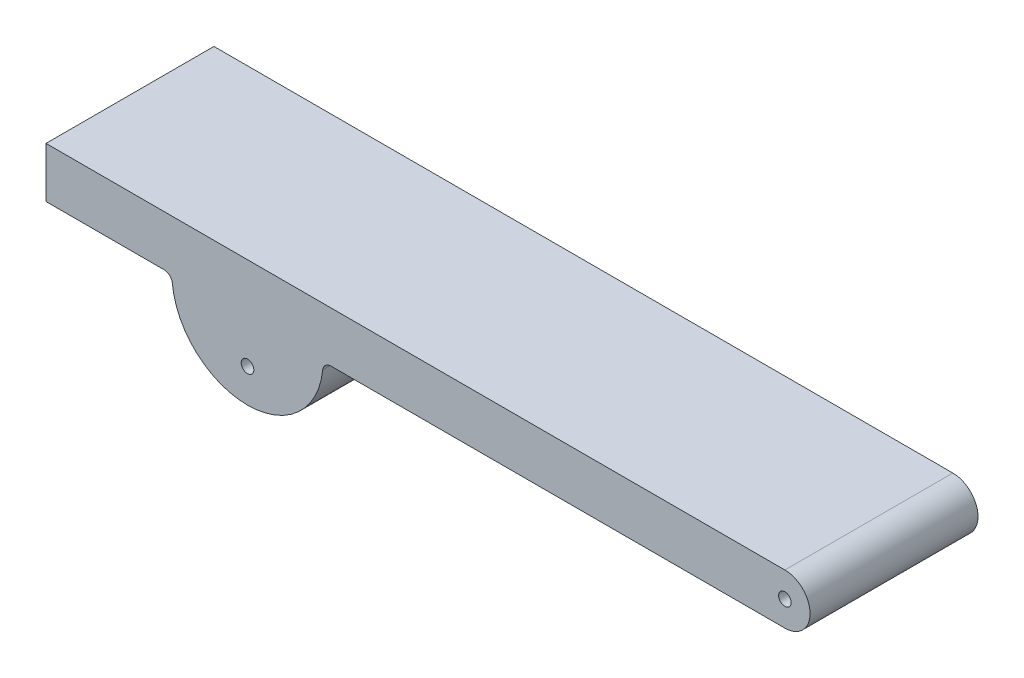
SolidWorks part; units mm, degrees
material "1.5714 (16NiCr4)"
ref_plane "Front Plane" through (0, 0, 0) normal (0, 0, 1) x (1, 0, 0)
ref_plane "Top Plane" through (0, 0, 0) normal (0, 1, 0) x (1, 0, 0)
ref_plane "Right Plane" through (0, 0, 0) normal (1, 0, 0) x (0, 0, -1)
sketch "Sketch1" plane through (0, 0, 0) normal (0, 0, 1) x (1, 0, 0)
  line L0 (440, 0) -> (-440, 0) construction
  line L1 (440, -30) -> (-440, -30)
  line L2 (440, 30) -> (290, 30)
  line L3 (440, 30) -> (440, -30)
  line L4 (200, 80) -> (200, 0) construction
  line L5 (110, 30) -> (-440, 30)
  arc A0 (110, 30) -> (290, 30) centre (200, 30) cw
  arc A1 (-440, 30) -> (-440, -30) centre (-440, 0) ccw
  point P3 (0, 0)
  dimension "D2" = 30
  dimension "D3" = 60
  dimension "D7" = 90
  dimension "D1" = 880
  dimension "D4" = 440
  dimension "D5" = 640
  dimension "D6" = 80
extrude "Boss-Extrude1" add sketch "Sketch1" along normal mid plane 200
sketch "Sketch2" plane through (0, 0, 100) normal (0, 0, 1) x (1, 0, 0)
  line L0 (200, 0) -> (200, 80) construction
  circle A0 centre (-440, 0) radius 7.5
  arc A1 (-440, 30) -> (-440, -30) centre (-440, 0) ccw construction
  circle A2 centre (200, 80) radius 7.5
  dimension "D1" = 15
  dimension "D4" = 15
  dimension "D2" = 80
  dimension "D3" = 640
extrude "Cut-Extrude1" cut sketch "Sketch2" against normal through all
fillet "Fillet1" radius 10 2 edges at (110, 30, 0) (290, 30, 0)
ref_axis "Axis2" through (0, 0, 16.5) along (0, 0, -1)
move or copy body "Body-Move/Copy1" bodies to move or copy 102 copy no rotation origin (0, 0, 0) rotation axis (0, 0, 1) rotation angle 180
